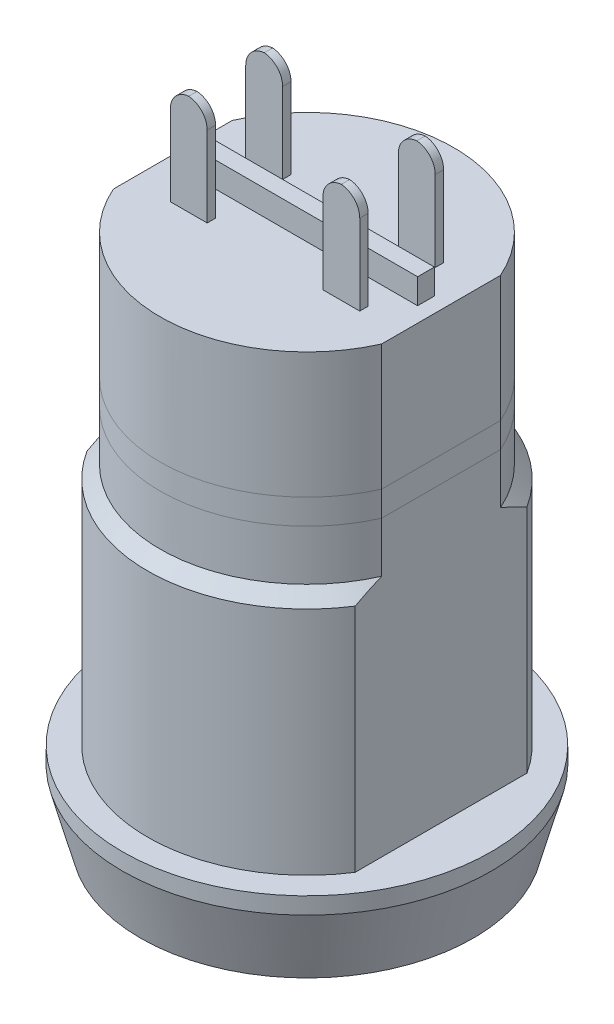
SolidWorks part; units mm, degrees
ref_plane "前视基准面" through (0, 0, 0) normal (0, 0, 1) x (1, 0, 0)
ref_plane "上视基准面" through (0, 0, 0) normal (0, 1, 0) x (1, 0, 0)
ref_plane "右视基准面" through (0, 0, 0) normal (1, 0, 0) x (0, 0, -1)
sketch "草图1" plane through (0, 0, 0) normal (0, 1, 0) x (1, 0, 0)
  circle A0 centre (0, 0) radius 11
  dimension "D1" = 22
extrude "拉伸1" add sketch "草图1" along normal blind 5
chamfer "倒角1" distance 4 angle 15 1 edges at (0, 0, 11) first distance on face at (0, 5, 11)
sketch "草图3" plane through (0, 5, 0) normal (0, 1, 0) x (-1, 0, 0)
  line L0 (-14.0419, 0) -> (17.3595, 0) construction
  line L1 (-8, 5.1235) -> (-8, -5.1235)
  line L2 (0, 14.0343) -> (0, -15.3362) construction
  line L3 (8, 5.1235) -> (8, -5.1235)
  arc A0 (-8, 5.1235) -> (8, 5.1235) centre (0, 0) cw
  arc A1 (-8, -5.1235) -> (8, -5.1235) centre (0, 0) ccw
  point P9 (-8, 0)
  point P13 (8, 0)
  dimension "D1" = 16
  dimension "D2" = 9.5
extrude "拉伸3" add sketch "草图3" along normal blind 26.5
sketch "草图4" plane through (0, 0, 0) normal (0, 1, 0) x (-1, 0, 0)
  line L0 (0, -6.2238) -> (0, 5.8769) construction
  line L1 (4.0827, 0) -> (-3.4119, 0) construction
  line L3 (1, -3.75) -> (-1, -3.75)
  line L4 (1, -3.75) -> (1, 3.75)
  line L5 (1, 3.75) -> (-1, 3.75)
  line L6 (-1, -3.75) -> (-1, 3.75)
  dimension "D1" = 2
  dimension "D2" = 7.5
extrude "切除-拉伸1" cut sketch "草图4" along normal blind 10
sketch "草图6" plane through (0, 31.5, 0) normal (0, 1, 0) x (1, 0, 0)
  line L0 (-15.0728, 0) -> (13.6512, 0) construction
  line L1 (0, 12.0256) -> (0, -12.4335) construction
  line L2 (3.45, 2.5) -> (3.45, 2)
  line L3 (-5.65, 2.5) -> (-3.45, 2.5)
  line L4 (-5.65, 2.5) -> (-5.65, 2)
  line L5 (-5.65, 2) -> (-3.45, 2)
  line L6 (-3.45, 2.5) -> (-3.45, 2)
  line L7 (5.65, 2) -> (3.45, 2)
  line L8 (5.65, 2.5) -> (5.65, 2)
  line L9 (5.65, 2.5) -> (3.45, 2.5)
  line L10 (5.65, -2.5) -> (3.45, -2.5)
  line L11 (5.65, -2.5) -> (5.65, -2)
  line L12 (5.65, -2) -> (3.45, -2)
  line L13 (-3.45, -2.5) -> (-3.45, -2)
  line L14 (-5.65, -2) -> (-3.45, -2)
  line L15 (-5.65, -2.5) -> (-5.65, -2)
  line L16 (-5.65, -2.5) -> (-3.45, -2.5)
  line L17 (3.45, -2.5) -> (3.45, -2)
  dimension "D1" = 2.2
  dimension "D2" = 0.5
  dimension "D3" = 5
  dimension "D4" = 11.3
extrude "凸台-拉伸1" add sketch "草图6" along normal blind 6
sketch "草图7" plane through (0, 31.5, 0) normal (0, 1, 0) x (1, 0, 0)
  line L0 (0, 11.5518) -> (0, -11.9596) construction
  line L1 (-12.4483, 0) -> (14.9999, 0) construction
  line L3 (-7.1, 0.5) -> (7.1, 0.5)
  line L4 (-7.1, 0.5) -> (-7.1, -0.5)
  line L5 (-7.1, -0.5) -> (7.1, -0.5)
  line L6 (7.1, 0.5) -> (7.1, -0.5)
  circle A0 centre (0, 0) radius 11 construction
  dimension "D1" = 1
  dimension "D3" = 14.2
extrude "凸台-拉伸2" add sketch "草图7" along normal blind 1.5
sketch "草图9" plane through (0, 31.5, 0) normal (0, 1, 0) x (1, 0, 0)
  circle A0 centre (0, 0) radius 8.75
  circle A1 centre (0, 0) radius 9.5
  dimension "D1" = 17.5
extrude "切除-拉伸2" cut sketch "草图9" against normal blind 12
chamfer "倒角2" distance 0.75 angle 45 2 edges at (0, 19.5, 9.5) (0, 19.5, -9.5)
sketch "草图10" plane through (-8, 0, 0) normal (-1, 0, 0) x (0, 0, 1)
  line L0 (8.75, 22.5) -> (-8.75, 22.5)
  line L1 (8.75, 19.5) -> (8.75, 31.5) construction
  line L2 (-8.75, 31.5) -> (-8.75, 19.5) construction
  line L3 (8.75, 24) -> (-8.75, 24)
  line L4 (-8.75, 19.5) -> (-3.5444, 19.5) construction
  dimension "D1" = 3
  dimension "D2" = 1.5
split line "分割线1"
sketch "草图11" plane through (0, 0, 0) normal (0, -1, 0) x (1, 0, 0)
  circle A0 centre (0, 0) radius 7.5
  dimension "D1" = 15
split line "分割线2"
fillet "圆角1" radius 1.2 8 edges at (-3.45, 37.5, -2.25) (-5.65, 37.5, -2.25) (3.45, 37.5, -2.25) (5.65, 37.5, -2.25) (5.65, 37.5, 2.25) (3.45, 37.5, 2.25) (-5.65, 37.5, 2.25) (-3.45, 37.5, 2.25)
